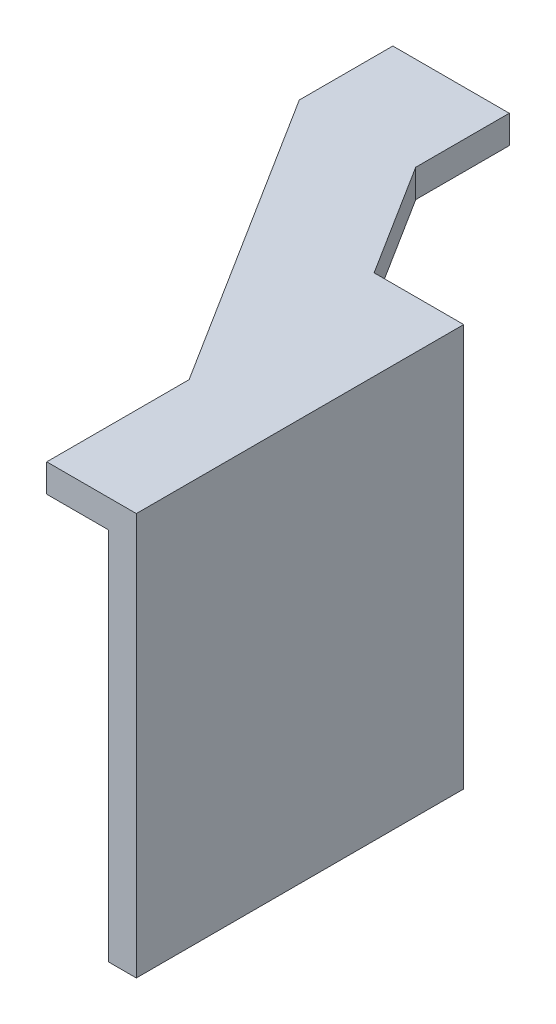
SolidWorks part; units mm, degrees
material "Perspex (TM) GS Acrylic Cast Sheet"
ref_plane "Front Plane" through (0, 0, 0) normal (0, 0, 1) x (1, 0, 0)
ref_plane "Top Plane" through (0, 0, 0) normal (0, 1, 0) x (1, 0, 0)
ref_plane "Right Plane" through (0, 0, 0) normal (1, 0, 0) x (0, 0, -1)
sketch "Sketch1" plane through (0, 0, 0) normal (0, 1, 0) x (1, 0, 0)
  line L0 (10, -5) -> (10, -52)
  line L1 (10, -5) -> (-10, -5)
  line L3 (10, 5) -> (-10, 5)
  line L4 (-10, -5) -> (-10, 5)
  line L5 (10, -5) -> (-10, 5) construction
  line L6 (10, 5) -> (-10, -5) construction
  line L7 (10, -52) -> (19.5785, -52)
  line L8 (19.5785, -52) -> (19.5785, 5)
  line L9 (19.5785, 5) -> (10, 5)
  point P0 (0, 0)
  dimension "D1" = 10
  dimension "D2" = 10
  dimension "D3" = 19.5785
  dimension "D4" = 52
extrude "Boss-Extrude1" add sketch "Sketch1" along normal blind 3
sketch "Sketch3" plane through (0, 0, 0) normal (0, -1, 0) x (1, 0, 0)
  line L0 (19.5785, 52) -> (19.5785, -5) construction
  line L1 (19.5785, 17) -> (16.5785, 17)
  line L2 (19.5785, 17) -> (19.5785, 52)
  line L3 (19.5785, 52) -> (16.5785, 52)
  line L4 (16.5785, 17) -> (16.5785, 52)
  line L5 (19.5785, 17) -> (16.5785, 52) construction
  line L6 (19.5785, 52) -> (16.5785, 17) construction
  line L7 (10, 52) -> (19.5785, 52) construction
  point P0 (18.0785, 34.5)
  dimension "D1" = 35
  dimension "D2" = 3
  dimension "D3" = 0
  dimension "5" = 0
extrude "Boss-Extrude2" add sketch "Sketch3" along normal blind 40
sketch "Sketch4" plane through (0, 0, 0) normal (0, 1, 0) x (1, 0, 0)
  line L0 (-10, 5) -> (-10, -5)
  line L1 (-10, -5) -> (19.5785, -52)
  line L2 (19.5785, -52) -> (19.5785, -17)
  line L3 (19.5785, -17) -> (10, -17)
  line L4 (10, -5) -> (10, -52) construction
  line L5 (-10, 5) -> (2.448, 5)
  line L6 (19.5785, 5) -> (-10, 5) construction
  line L10 (2.448, 5) -> (2.448, -5)
  line L11 (-10, -5) -> (10, -5) construction
  line L12 (2.448, -5) -> (10, -17)
extrude "Boss-Extrude3" add sketch "Sketch4" along normal blind 3
sketch "Sketch5" plane through (0, 0, 0) normal (0, 1, 0) x (1, 0, 0)
  line L3 (19.5785, 5) -> (-10, 5) construction
  line L4 (2.448, 5) -> (19.5785, 5)
  line L5 (19.5785, 5) -> (19.5785, -17)
  line L7 (2.448, -5) -> (2.448, 5)
  line L8 (19.5785, -17) -> (10, -17)
  line L9 (10, -17) -> (2.448, -5)
  line L10 (10, -17) -> (2.448, -5) construction
extrude "Cut-Extrude3" cut sketch "Sketch5" against normal mid plane 13
